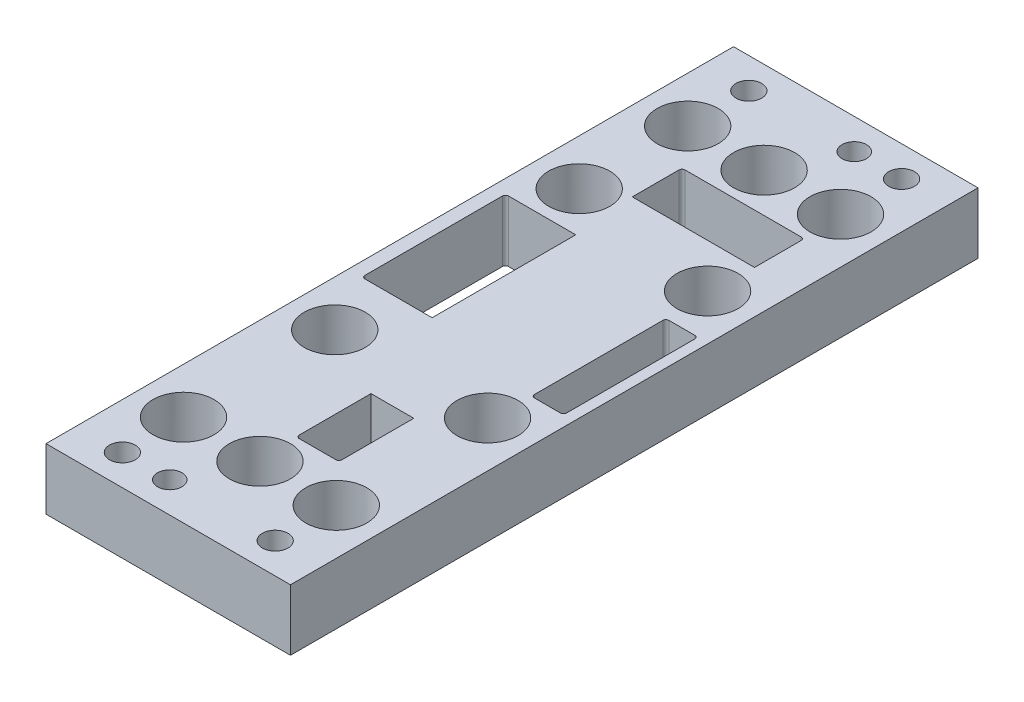
SolidWorks part; units mm, degrees
material "Plain Carbon Steel"
ref_plane "Front Plane" through (0, 0, 0) normal (0, 0, 1) x (1, 0, 0)
ref_plane "Top Plane" through (0, 0, 0) normal (0, 1, 0) x (1, 0, 0)
ref_plane "Right Plane" through (0, 0, 0) normal (1, 0, 0) x (0, 0, -1)
sketch "Sketch1" plane through (0, 0, 0) normal (0, 1, 0) x (1, 0, 0)
  line L0 (-46, 0) -> (34, 0) construction
  line L1 (-46, -112.5) -> (34, -112.5)
  line L2 (-46, -112.5) -> (-46, 112.5)
  line L3 (-46, 112.5) -> (34, 112.5)
  line L4 (34, -112.5) -> (34, 112.5)
  dimension "D1" = 34
  dimension "D2" = 46
  dimension "D3" = 225
extrude "Boss-Extrude1" add sketch "Sketch1" against normal blind 20
sketch "Sketch2" plane through (0, 0, 0) normal (0, 1, 0) x (1, 0, 0)
  line L0 (18, -9.64) -> (29.5, -9.64) construction
  line L1 (29.5, 14.36) -> (18, 14.36) construction
  line L2 (30.5, -8.64) -> (30.5, 13.36) construction
  line L3 (20, -9.64) -> (29.5, -9.64) construction
  line L4 (29.5, 14.36) -> (20, 14.36) construction
  line L5 (30.5, -8.64) -> (30.5, 13.36) construction
  line L6 (20, 14.36) -> (20, -9.64) construction
  line L7 (22, -9.64) -> (22, 14.36) construction
  line L9 (21, -19.64) -> (29.5, -19.64)
  line L10 (20, -18.64) -> (20, 23.36)
  line L11 (21, 24.36) -> (29.5, 24.36)
  line L12 (30.5, -18.64) -> (30.5, 23.36)
  arc A0 (29.5, -9.64) -> (30.5, -8.64) centre (29.5, -8.64) ccw construction
  arc A1 (30.5, 13.36) -> (29.5, 14.36) centre (29.5, 13.36) ccw construction
  arc A2 (29.5, -9.64) -> (30.5, -8.64) centre (29.5, -8.64) ccw construction
  arc A3 (30.5, 13.36) -> (29.5, 14.36) centre (29.5, 13.36) ccw construction
  arc A4 (21, -19.64) -> (20, -18.64) centre (21, -18.64) cw
  arc A5 (29.5, -19.64) -> (30.5, -18.64) centre (29.5, -18.64) ccw
  arc A6 (29.5, 24.36) -> (30.5, 23.36) centre (29.5, 23.36) cw
  arc A7 (20, 23.36) -> (21, 24.36) centre (21, 23.36) cw
  dimension "D6" = 1
  dimension "D1" = 2
  dimension "D2" = 10.5
  dimension "D3" = 24
  dimension "D4" = 10
  dimension "D5" = 10
extrude "Cut-Extrude1" cut sketch "Sketch2" against normal up to next
sketch "Sketch4" plane through (0, 0, 0) normal (0, 1, 0) x (1, 0, 0)
  line L0 (7, -68.64) -> (7, -43.14) construction
  line L2 (-7, -43.14) -> (-7, -68.64) construction
  line L3 (-6, -69.64) -> (6, -69.64) construction
  line L4 (7, -68.64) -> (7, -45.14)
  line L5 (7, -45.14) -> (-7, -45.14)
  line L6 (-7, -45.14) -> (-7, -68.64)
  line L7 (-6, -69.64) -> (6, -69.64)
  line L8 (-7, -47.14) -> (7, -47.14) construction
  arc A2 (-7, -68.64) -> (-6, -69.64) centre (-6, -68.64) ccw construction
  arc A3 (6, -69.64) -> (7, -68.64) centre (6, -68.64) ccw construction
  arc A6 (-7, -68.64) -> (-6, -69.64) centre (-6, -68.64) ccw
  arc A7 (6, -69.64) -> (7, -68.64) centre (6, -68.64) ccw
  dimension "D1" = 2
extrude "Cut-Extrude2" cut sketch "Sketch4" against normal up to next
sketch "Sketch5" plane through (0, 0, 0) normal (0, 1, 0) x (1, 0, 0)
  line L1 (-16.5, 33.36) -> (-40.5, 33.36) construction
  line L2 (-41.5, 32.36) -> (-41.5, -12.64) construction
  line L3 (-40.5, -13.64) -> (-16.5, -13.64) construction
  line L4 (-18.5, -13.64) -> (-18.5, 33.36)
  line L5 (-18.5, 33.36) -> (-40.5, 33.36)
  line L6 (-41.5, 32.36) -> (-41.5, -12.64)
  line L7 (-40.5, -13.64) -> (-18.5, -13.64)
  line L8 (-20.5, 33.36) -> (-20.5, -13.64) construction
  arc A2 (-40.5, 33.36) -> (-41.5, 32.36) centre (-40.5, 32.36) ccw construction
  arc A3 (-41.5, -12.64) -> (-40.5, -13.64) centre (-40.5, -12.64) ccw construction
  arc A6 (-40.5, 33.36) -> (-41.5, 32.36) centre (-40.5, 32.36) ccw
  arc A7 (-41.5, -12.64) -> (-40.5, -13.64) centre (-40.5, -12.64) ccw
  dimension "D1" = 2
extrude "Cut-Extrude3" cut sketch "Sketch5" against normal up to next
sketch "Sketch6" plane through (0, 0, 0) normal (0, 1, 0) x (1, 0, 0)
  line L0 (19, 69.64) -> (-19, 69.64) construction
  line L1 (-20, 68.64) -> (-20, 51.36) construction
  line L3 (20, 51.36) -> (20, 68.64) construction
  line L4 (19, 69.64) -> (-19, 69.64)
  line L5 (-20, 68.64) -> (-20, 53.36)
  line L6 (-20, 53.36) -> (20, 53.36)
  line L7 (20, 53.36) -> (20, 68.64)
  line L8 (-20, 55.36) -> (20, 55.36) construction
  arc A0 (20, 68.64) -> (19, 69.64) centre (19, 68.64) ccw construction
  arc A1 (-19, 69.64) -> (-20, 68.64) centre (-19, 68.64) ccw construction
  arc A4 (20, 68.64) -> (19, 69.64) centre (19, 68.64) ccw
  arc A5 (-19, 69.64) -> (-20, 68.64) centre (-19, 68.64) ccw
  dimension "D1" = 2
extrude "Cut-Extrude4" cut sketch "Sketch6" against normal up to next
hole_wizard "CBORE for M8 Hex Socket Head Cap Screw1" positions "Sketch10" profile "Sketch9" counterbore size "M8" standard "ISO" end condition through all
sketch "Sketch10" plane through (0, -20, 0) normal (0, -1, 0) x (-1, 0, 0)
  line L0 (-34, 112.5) -> (46, 112.5) construction
  line L1 (-34, -112.5) -> (-34, 112.5) construction
  line L2 (46, 112.5) -> (46, -112.5) construction
  line L3 (46, -112.5) -> (-34, -112.5) construction
  point P0 (-19, 102.5)
  point P2 (31, 102.5)
  point P4 (-19, -102.5)
  point P6 (31, -102.5)
  point P17 (-20.696, 91.4236)
  point P18 (0, 0)
  point P25 (0, 0)
  point P26 (0, 0)
  point P27 (0, 0)
  point P28 (0, 0)
  dimension "D1" = 10
  dimension "D2" = 15
  dimension "D3" = 15
  dimension "D4" = 10
sketch "Sketch9" plane through (19, -20, -102.5) normal (1, 0, 0) x (0, 0, -1)
  line L0 (0, 0) -> (0, 20)
  line L1 (0, 20) -> (4.2, 20)
  line L3 (4.2, 20) -> (4.2, 8.6)
  line L4 (4.2, 8.6) -> (7.5, 8.6)
  line L5 (7.5, 8.6) -> (7.5, 0)
  line L7 (7.5, 0) -> (0, 0)
  line L11 (0, -6.35) -> (0, 107.95) construction
  dimension "Thru Hole Dia." = 8.4
  dimension "Thru Hole Depth" = 20
  dimension "C'Bore Dia." = 15
  dimension "C'Bore Depth" = 8.6
hole_wizard "Ø8.0mm Dowel Hole1" positions "Sketch13" profile "Sketch12" hole size "Ø8.0" standard "ISO" end condition through all
sketch "Sketch13" plane through (0, -20, 0) normal (0, -1, 0) x (-1, 0, 0)
  line L0 (-34, 112.5) -> (46, 112.5) construction
  line L1 (46, -112.5) -> (-34, -112.5) construction
  circle A0 centre (-19, 102.5) radius 7.5 construction
  circle A1 centre (31, -102.5) radius 7.5 construction
  point P0 (-3.5, 102.5)
  point P2 (15.5, -102.5)
  dimension "D1" = 8
  dimension "D3" = 8
  dimension "D2" = 10
  dimension "D4" = 10
sketch "Sketch12" plane through (3.5, -20, -102.5) normal (1, 0, 0) x (0, 0, -1)
  line L0 (0, 0) -> (0, 20)
  line L1 (0, 20) -> (4, 20)
  line L2 (4, 20) -> (4, 0)
  line L5 (4, 0) -> (0, 0)
  line L11 (0, -6.35) -> (0, 107.95) construction
  dimension "Thru Hole Dia." = 8
  dimension "Thru Hole Depth" = 20
sketch "Sketch7" plane through (0, 0, 0) normal (0, 1, 0) x (1, 0, 0)
  line L0 (-46, 112.5) -> (-46, -112.5) construction
  line L1 (34, -112.5) -> (34, 112.5) construction
  line L2 (-6, 112.5) -> (-6, -112.5) construction
  line L3 (34, 112.5) -> (-46, 112.5) construction
  line L4 (-46, -112.5) -> (34, -112.5) construction
  line L5 (-46, 0) -> (34, 0) construction
  circle A1 centre (-31, -33) radius 10
  circle A2 centre (-6, 82.5) radius 10
  circle A3 centre (19, -33) radius 10
  circle A4 centre (-31, 47) radius 10
  circle A5 centre (19, 39) radius 10
  circle A7 centre (-31, -82.5) radius 10
  circle A8 centre (-6, -82.5) radius 10
  circle A10 centre (19, -82.5) radius 10
  circle A11 centre (-31, 82.5) radius 10
  circle A14 centre (19, 82.5) radius 10
  point P2 (0, 0)
  point P11 (0, 0)
  dimension "D1" = 15
  dimension "D9" = 20
  dimension "D2" = 15
  dimension "D3" = 30
  dimension "D4" = 30
  dimension "D5" = 47
  dimension "D6" = 39
  dimension "D8" = 33
extrude "Cut-Extrude5" cut sketch "Sketch7" against normal up to next
